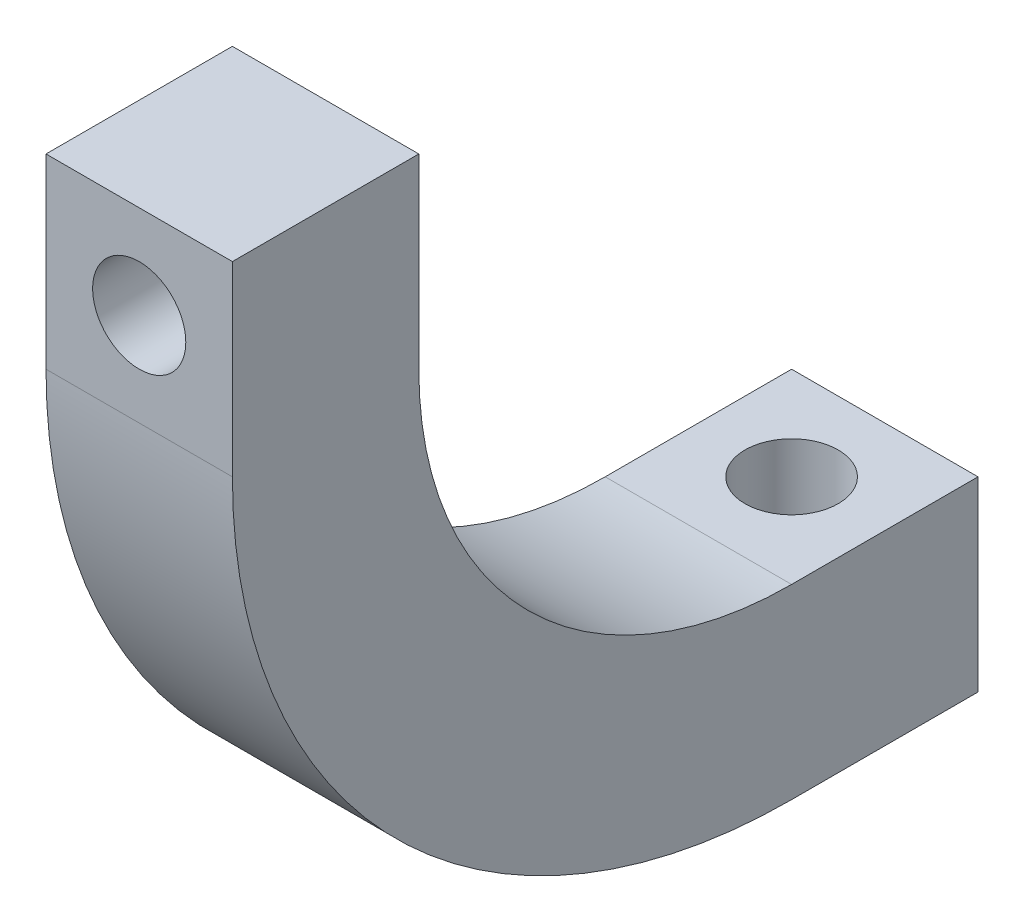
SolidWorks part; units mm, degrees
ref_plane "Front Plane" through (0, 0, 0) normal (0, 0, 1) x (1, 0, 0)
ref_plane "Top Plane" through (0, 0, 0) normal (0, 1, 0) x (1, 0, 0)
ref_plane "Right Plane" through (0, 0, 0) normal (1, 0, 0) x (0, 0, -1)
ref_axis "Z" through (0, 0, 22.75) along (0, 0, -1)
sketch "Sketch4" plane through (0, 0, 0) normal (0, 0, 1) x (1, 0, 0)
  circle A0 centre (0, 0) radius 14 construction
  dimension "D1" = 28
sketch "Sketch5" plane through (0, 0, 0) normal (1, 0, 0) x (0, 0, -1)
  line L0 (-15, 3) -> (-15, 0)
  line L1 (-15, 0) -> (-15, -3)
  line L2 (-21, -3) -> (-21, 3)
  line L6 (-21, 3) -> (-15, 3)
  line L12 (-22.75, 0) -> (-13.0351, 0) construction
  line L13 (0, 0) -> (-14.9091, -14.9091) construction
  line L14 (0, 0) -> (7.0065, 0) construction
  line L15 (0, -15) -> (-3, -15)
  line L16 (3, -15) -> (0, -15)
  line L17 (-3, -21) -> (3, -21)
  line L18 (3, -21) -> (3, -15)
  circle A0 centre (0, 0) radius 14 construction
  arc A1 (-15, -3) -> (-3, -15) centre (-3, -3) ccw
  arc A2 (-21, -3) -> (-3, -21) centre (-3, -3) ccw
  point P2 (9.4307, -21)
  point P4 (0, -2.1363)
  point P20 (-20.5214, -4.6985)
  point P22 (-36.7289, 3)
  dimension "D1" = 28
  dimension "D4" = 3
  dimension "D2" = 45
  dimension "D3" = 6
  dimension "D5" = 15
sketch "Sketch6" plane through (0, 0, 0) normal (0, 1, 0) x (1, 0, 0)
  circle A0 centre (0, 0) radius 14 construction
  dimension "D1" = 28
extrude "Boss-Extrude1" add sketch "Sketch5" along normal blind 3 and the other way blind 3
sketch "Sketch7" plane through (0, 0, 0) normal (0, 0, 1) x (1, 0, 0)
  circle A0 centre (0, 0) radius 1.5
  dimension "D1" = 3
extrude "Cut-Extrude1" cut sketch "Sketch7" along normal through all
sketch "Sketch8" plane through (0, 0, 0) normal (0, 1, 0) x (1, 0, 0)
  circle A0 centre (0, 0) radius 1.5
  dimension "D1" = 3
extrude "Cut-Extrude2" cut sketch "Sketch8" against normal through all
ref_axis "Y" through (0, -9.3489, 0) along (0, -1, 0)
equation "\"rbracket-width\"= \"L2Thickness\""
equation "\"EyeCaptureRadius\"= ( \"EyeDiameter\" + \"EyeClearance\" ) / 2"
equation "\"rbracket_planetocenterline_dist\"= \"BasePlaneDistance\""
equation "\"EyeDiameter\" = 28"
equation "\"BasePlaneDistance\" = 45"
equation "\"EyeClearance\" = 2"
equation "\"D1@Sketch4\"=\"EyeDiameter\""
equation "\"D1@Sketch6\"=\"EyeDiameter\""
equation "\"D1@Boss-Extrude1\"=\"rbracket-width\"/2"
equation "\"D2@Boss-Extrude1\"=\"rbracket-width\"/2"
equation "\"L2Thickness\" = 6"
equation "\"D3@Sketch5\"=\"L2Thickness\""
equation "\"D5@Sketch5\"=(\"EyeDiameter\"+\"EyeClearance\")/2"
